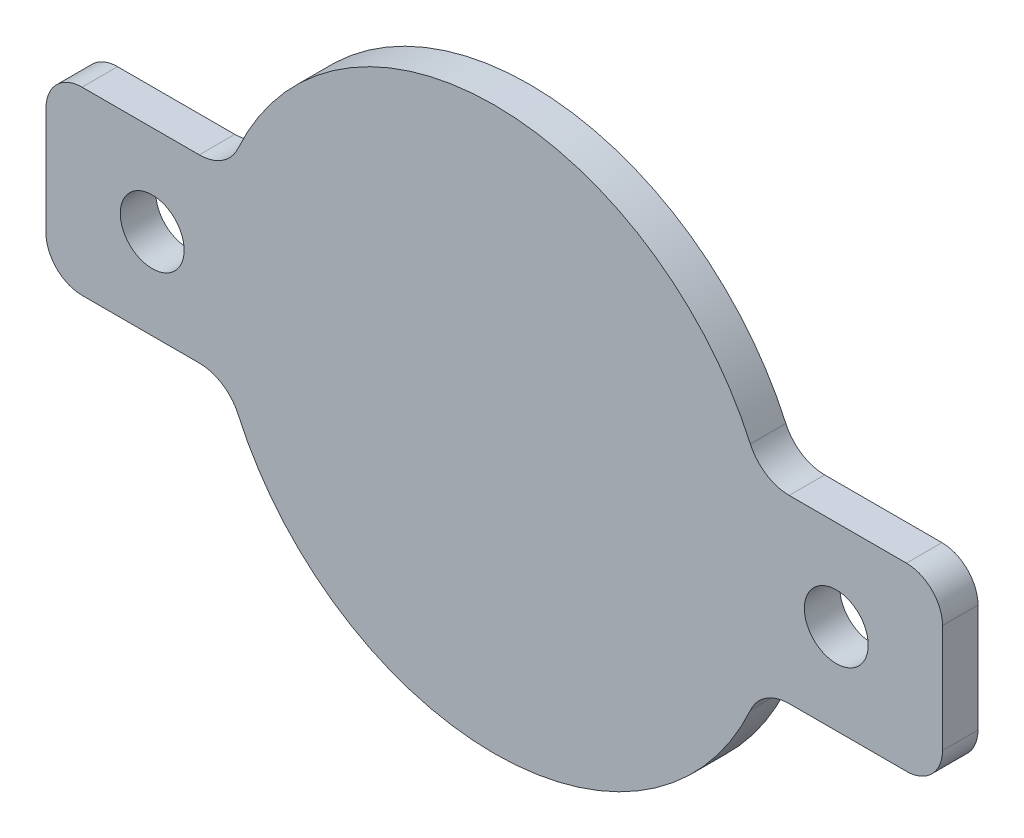
SolidWorks part; units mm, degrees
material "ABS"
ref_plane "X-Y Datum" through (0, 0, 0) normal (0, 0, 1) x (1, 0, 0)
ref_plane "X-Z Datum" through (0, 0, 0) normal (0, 1, 0) x (1, 0, 0)
ref_plane "Y-Z Datum" through (0, 0, 0) normal (1, 0, 0) x (0, 0, -1)
sketch "Sketch1" plane through (0, 0, 0) normal (0, 0, 1) x (-1, 0, 0)
  line L6 (-16.0929, 4.1604) -> (-31.0539, 4.1604)
  line L7 (-31.0539, 4.1604) -> (-31.0539, -8.5396)
  line L8 (-31.0539, -8.5396) -> (-16.0929, -8.5396)
  line L9 (17.122, 4.1604) -> (32.083, 4.1604)
  line L10 (32.083, 4.1604) -> (32.083, -8.5396)
  line L11 (32.083, -8.5396) -> (17.122, -8.5396)
  arc A2 (-16.0929, -8.5396) -> (17.122, -8.5396) centre (0.5145, -2.1896) ccw
  circle A3 centre (-23.5734, -2.1896) radius 2.625
  circle A4 centre (24.6025, -2.1896) radius 2.625
  arc A5 (17.122, 4.1604) -> (-16.0929, 4.1604) centre (0.5145, -2.1896) ccw
extrude "Boss-Extrude1" add sketch "Sketch1" along normal blind 2.5 contours A3 | A4 | L9 A5 L6 L7 L8 A2 L11 L10 A3 A4 region at (-0.5145, 2.1896, 0) region at (23.5734, 2.1896, 0) region at (-24.6025, 2.1896, 0)
fillet "Fillet1" radius 2.54 8 edges at (16.0929, 8.5396, 1.25) (-17.122, 8.5396, 1.25) (-17.122, -4.1604, 1.25) (16.0929, -4.1604, 1.25) (-32.083, -4.1604, 1.25) (-32.083, 8.5396, 1.25) (31.0539, 8.5396, 1.25) (31.0539, -4.1604, 1.25)
hole_wizard "M4 Clearance Hole1" positions "Sketch2" profile "Sketch3" hole size "M4" standard "ANSI Metric" end condition through all
sketch "Sketch2" plane through (0, 0, 2.5) normal (0, 0, 1) x (1, 0, 0)
  point P7 (-24.6025, 2.1896)
  point P10 (23.5734, 2.1896)
sketch "Sketch3" plane through (-24.6025, 2.1896, 2.5) normal (1, 0, 0) x (0, -1, 0)
  line L0 (0, 0) -> (0, 2.5)
  line L1 (0, 2.5) -> (2.25, 2.5)
  line L2 (2.25, 2.5) -> (2.25, 0)
  line L5 (2.25, 0) -> (0, 0)
  line L11 (0, -6.35) -> (0, 107.95) construction
  dimension "Thru Hole Dia." = 4.5
  dimension "Thru Hole Depth" = 2.5
sketch "Sketch4" plane through (0, 0, 2.5) normal (0, 0, 1) x (1, 0, 0)
  circle A2 centre (-0.5145, 2.1896) radius 19.78
  arc A3 (15.4736, 9.9683) -> (-16.5026, 9.9683) centre (-0.5145, 2.1896) ccw construction
  arc A4 (15.4736, 9.9683) -> (-16.5026, 9.9683) centre (-0.5145, 2.1896) ccw
  point P0 (-0.5145, 2.1896)
  line M6 (-29.543, -4.1604) -> (-18.7867, -4.1604)
  arc M7 (-18.7867, -4.1604) -> (-16.5026, -5.5892) centre (-18.7867, -6.7004) cw
  arc M8 (-16.5026, -5.5892) -> (15.4736, -5.5892) centre (-0.5145, 2.1896) ccw
  arc M9 (15.4736, -5.5892) -> (17.7576, -4.1604) centre (17.7576, -6.7004) cw
  line M10 (17.7576, -4.1604) -> (28.5139, -4.1604)
  line M14 (28.5139, 8.5396) -> (17.7576, 8.5396)
  arc M15 (17.7576, 8.5396) -> (15.4736, 9.9683) centre (17.7576, 11.0796) cw
  arc M16 (15.4736, 9.9683) -> (-16.5026, 9.9683) centre (-0.5145, 2.1896) ccw
  arc M17 (-16.5026, 9.9683) -> (-18.7867, 8.5396) centre (-18.7867, 11.0796) cw
  line M18 (-18.7867, 8.5396) -> (-29.543, 8.5396)
  dimension "D1" = 2
extrude "Boss-Extrude2" add sketch "Sketch4" against normal blind 2.5 separate body contours A2 M6 M10 M9 M8 M7 | A2 M14 M18 M17 M16 M15 region at (17.988, 8.9376, 2.5) region at (-0.5145, -17.1924, 2.5)
combine bodies "Combine1" operation type add bodies to combine 102 103 104
fillet "Fillet2" radius 3 4 edges at (18.2185, -4.1604, 1.25) (18.2185, 8.5396, 1.25) (-19.2476, -4.1604, 1.25) (-19.2476, 8.5396, 1.25)
